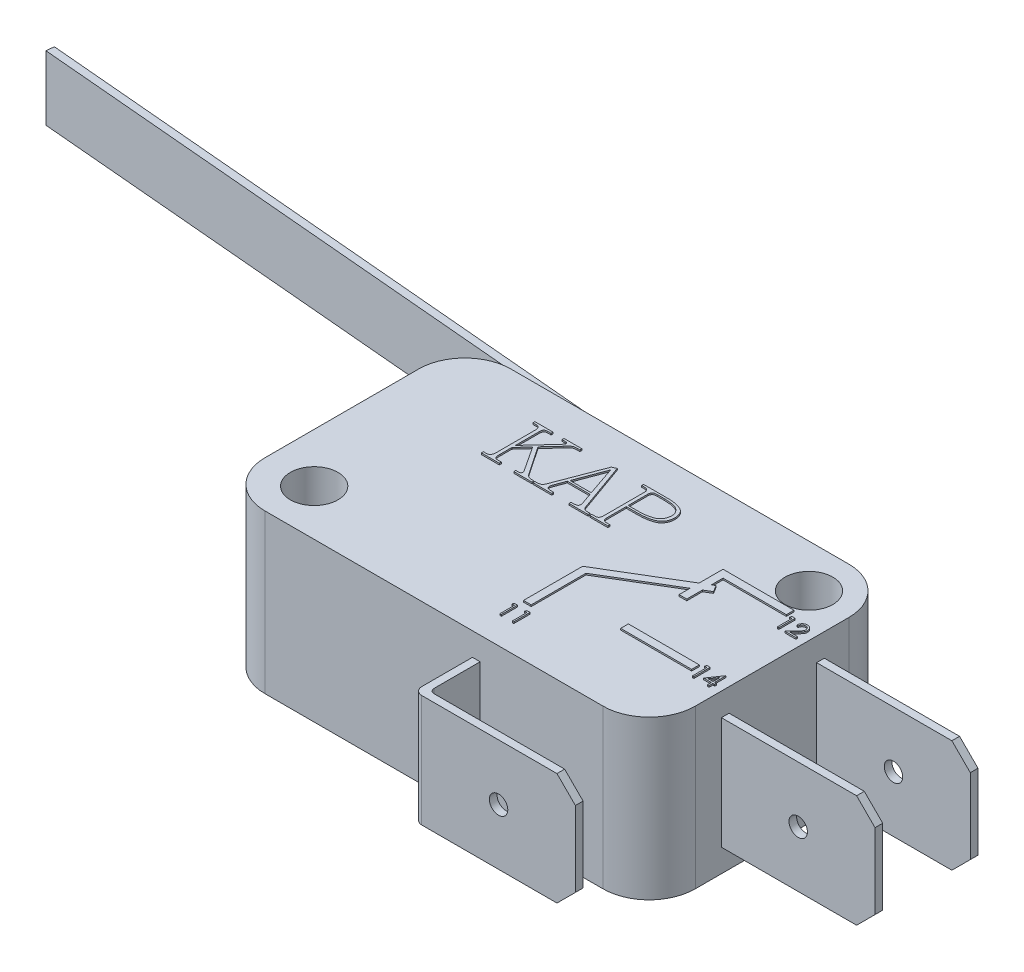
SolidWorks part; units mm, degrees
ref_plane "Plano frontal" through (0, 0, 0) normal (0, 0, 1) x (1, 0, 0)
ref_plane "Plano superior" through (0, 0, 0) normal (0, 1, 0) x (1, 0, 0)
ref_plane "Plano direito" through (0, 0, 0) normal (1, 0, 0) x (0, 0, -1)
sketch "Esboço1" plane through (0, 0, 0) normal (0, 1, 0) x (1, 0, 0)
  line L1 (-68.1435, 2.0444) -> (-40.1435, 2.0444)
  line L2 (-68.1435, 2.0444) -> (-68.1435, -13.9556)
  line L3 (-68.1435, -13.9556) -> (-40.1435, -13.9556)
  line L4 (-40.1435, 2.0444) -> (-40.1435, -13.9556)
extrude "Ressalto-extrusão2" add sketch "Esboço1" along normal blind 10.3
fillet "Filete2" radius 3 1 edges at (-40.1435, 5.15, -2.0444)
fillet "Filete3" radius 3 1 edges at (-40.1435, 5.15, 13.9556)
fillet "Filete4" radius 3 1 edges at (-68.1435, 5.15, -2.0444)
fillet "Filete5" radius 3 1 edges at (-68.1435, 5.15, 13.9556)
sketch "Esboço2" plane through (0, 10.3, 0) normal (0, 1, 0) x (1, 0, 0)
  line L0 (-40.1435, -10.9556) -> (-40.1435, -0.9556) construction
  line L1 (-43.1435, 2.0444) -> (-65.1435, 2.0444) construction
  circle A0 centre (-64.9435, -10.9556) radius 1.55
  circle A1 centre (-42.9435, -0.7556) radius 1.55
  dimension "D1" = 3.1
  dimension "D2" = 3.1
  dimension "D4" = 2.8
  dimension "D5" = 22
  dimension "D6" = 10.2
  dimension "D3" = 2.8
extrude "Corte-extrusão1" cut sketch "Esboço2" against normal blind 10.3
sketch "Esboço3" plane through (-40.1435, 0, 0) normal (1, 0, 0) x (0, 0, -1)
  line L0 (-10.9556, 10.3) -> (-0.9556, 10.3) construction
  line L1 (-2.5556, 8.8) -> (-3.0556, 8.8)
  line L2 (-2.5556, 8.8) -> (-2.5556, 1.5)
  line L3 (-2.5556, 1.5) -> (-3.0556, 1.5)
  line L4 (-3.0556, 8.8) -> (-3.0556, 1.5)
  line L5 (-10.9556, 0) -> (-0.9556, 0) construction
  line L6 (-0.9556, 0) -> (-0.9556, 10.3) construction
  line L8 (-8.7556, 8.8) -> (-9.2556, 8.8)
  line L9 (-8.7556, 8.8) -> (-8.7556, 1.5)
  line L10 (-8.7556, 1.5) -> (-9.2556, 1.5)
  line L11 (-9.2556, 8.8) -> (-9.2556, 1.5)
  line L13 (-10.9556, 10.3) -> (-10.9556, 0) construction
  dimension "D1" = 1.5
  dimension "D2" = 1.5
  dimension "D3" = 1.6
  dimension "D4" = 0.5
  dimension "D5" = 0.5
  dimension "D6" = 5.7
  dimension "D7" = 1.7
extrude "Ressalto-extrusão3" add sketch "Esboço3" along normal blind 10
sketch "Esboço4" plane through (0, 0, 13.9556) normal (0, 0, 1) x (1, 0, 0)
  line L0 (-65.1435, 10.3) -> (-43.1435, 10.3) construction
  line L1 (-51.6435, 8.8) -> (-51.1435, 8.8)
  line L2 (-51.6435, 8.8) -> (-51.6435, 1.5)
  line L3 (-51.6435, 1.5) -> (-51.1435, 1.5)
  line L4 (-51.1435, 8.8) -> (-51.1435, 1.5)
  line L5 (-65.1435, 0) -> (-43.1435, 0) construction
  line L6 (-43.1435, 0) -> (-43.1435, 10.3) construction
  dimension "D1" = 0.5
  dimension "D2" = 1.5
  dimension "D3" = 1.5
  dimension "D4" = 8
extrude "Ressalto-extrusão4" add sketch "Esboço4" along normal blind 3.8
sketch "Esboço5" plane through (-51.1435, 0, 0) normal (1, 0, 0) x (0, 0, -1)
  line L0 (-17.7556, 1.5) -> (-13.9556, 1.5) construction
  line L1 (-17.7556, 8.8) -> (-17.2556, 8.8)
  line L2 (-17.7556, 8.8) -> (-17.7556, 1.5)
  line L3 (-17.7556, 1.5) -> (-17.2556, 1.5)
  line L4 (-17.2556, 8.8) -> (-17.2556, 1.5)
  dimension "D1" = 0.5
extrude "Ressalto-extrusão5" add sketch "Esboço5" along normal blind 10
fillet "Filete8" radius 0.5 1 edges at (-51.6435, 5.15, 17.7556)
fillet "Filete9" radius 0.3 1 edges at (-51.1435, 5.15, 17.2556)
sketch "Esboço6" plane through (0, 0, -2.0444) normal (0, 0, -1) x (-1, 0, 0)
  line L1 (51.4435, 3.05) -> (50.9435, 3.05)
  line L2 (51.4435, 3.05) -> (51.4435, 7.25)
  line L3 (51.4435, 7.25) -> (50.9435, 7.25)
  line L4 (50.9435, 3.05) -> (50.9435, 7.25)
  line L6 (43.1435, 10.3) -> (43.1435, 0) construction
  line L7 (51.4435, 5.15) -> (65.1435, 5.15) construction
  line L8 (65.1435, 0) -> (65.1435, 10.3) construction
  dimension "D1" = 4.2
  dimension "D3" = 0.5
  dimension "D4" = 7.8
extrude "Ressalto-extrusão6" add sketch "Esboço6" along normal blind 2
sketch "Esboço10" plane through (0, 0, -2.0444) normal (0, 0, -1) x (-1, 0, 0)
  line L0 (62.9134, 5.15) -> (65.1435, 5.15) construction
  line L1 (62.9134, 2.9) -> (60.0481, 2.9)
  line L2 (62.9134, 2.9) -> (62.9134, 7.4)
  line L3 (62.9134, 7.4) -> (60.0481, 7.4)
  line L4 (60.0481, 2.9) -> (60.0481, 7.4)
  line L5 (65.1435, 0) -> (65.1435, 10.3) construction
  dimension "D1" = 4.5
extrude "Ressalto-extrusão7" add sketch "Esboço10" along normal blind 1.9
fillet "Filete11" radius 0.6 2 edges at (-60.0481, 5.15, -3.9444) (-62.9134, 5.15, -3.9444)
chamfer "Chanfro1" distance 0.5 angle 5 1 edges at (-51.4435, 5.15, -4.0444) first distance on face at (-51.4435, 5.15, -3.0444)
sketch "Esboço12" plane through (-51.3604, 0, -4.4935) normal (-0.9962, 0, -0.0872) x (-0.0872, 0, 0.9962)
  line L1 (0.4507, 3.05) -> (0.9527, 3.05)
  line L2 (0.4507, 3.05) -> (0.4507, 7.25)
  line L3 (0.4507, 7.25) -> (0.9527, 7.25)
  line L4 (0.9527, 3.05) -> (0.9527, 7.25)
extrude "Ressalto-extrusão8" add sketch "Esboço12" along normal blind 50
chamfer "Chanfro2" distance 1.2 angle 45 6 edges at (-41.1435, 8.8, 17.5056) (-41.1435, 1.5, 17.5056) (-30.1435, 8.8, 9.0056) (-30.1435, 8.8, 2.8056) (-30.1435, 1.5, 9.0056) (-30.1435, 1.5, 2.8056)
sketch "Esboço13" plane through (0, 0, 2.5556) normal (0, 0, -1) x (-1, 0, 0)
  line L0 (30.1435, 5.15) -> (40.1435, 5.15) construction
  line L1 (30.1435, 2.7) -> (30.1435, 7.6) construction
  line L2 (40.1435, 1.5) -> (40.1435, 8.8) construction
  circle A0 centre (35.1435, 5.15) radius 0.6
  dimension "D1" = 1.2
  dimension "D2" = 5
extrude "Corte-extrusão2" cut sketch "Esboço13" against normal blind 10
sketch "Esboço14" plane through (0, 0, 17.7556) normal (0, 0, 1) x (1, 0, 0)
  line L0 (-41.1435, 5.15) -> (-51.1435, 5.15) construction
  line L1 (-41.1435, 7.6) -> (-41.1435, 2.7) construction
  line L2 (-51.1435, 8.8) -> (-51.1435, 1.5) construction
  circle A0 centre (-46.1435, 5.15) radius 0.6
  dimension "D1" = 1.2
extrude "Corte-extrusão3" cut sketch "Esboço14" against normal up to next
sketch "Esboço15" plane through (0, 10.3, 0) normal (0, 1, 0) x (1, 0, 0)
  text T0 "KAP\r\n" font "@Adobe Ming Std L" height 3.5
extrude "Ressalto-extrusão9" add sketch "Esboço15" along normal blind 0.1
sketch "Esboço16" plane through (0, 0, 0) normal (0, -1, 0) x (1, 0, 0)
  text T0 "MV7"
extrude "Corte-extrusão4" cut sketch "Esboço16" against normal blind 0.1
sketch "Esboço17" plane through (0, 0, 0) normal (0, -1, 0) x (1, 0, 0)
  text T0 "15A 250VAC\r\n15(3A) 250~\r\nT85" font "Century Gothic" height in points 5
extrude "Corte-extrusão5" cut sketch "Esboço17" against normal blind 0.1
sketch "Esboço18" plane through (0, 10.3, 0) normal (0, 1, 0) x (1, 0, 0)
  line L0 (-46.8547, -5.2963) -> (-46.8547, -4.5807)
  line L1 (-46.8547, -2.4369) -> (-42.2356, -2.4369)
  line L2 (-42.2356, -9.0985) -> (-46.8547, -9.0985)
  line L3 (-51.5907, -10.6853) -> (-51.5907, -6.8392)
  line L4 (-51.5907, -6.8392) -> (-46.8547, -3.9976)
  line L5 (-51.0907, -10.6853) -> (-51.0907, -7.1223)
  line L6 (-51.0907, -7.1223) -> (-46.8547, -4.5807)
  line L7 (-42.2356, -8.5985) -> (-46.8547, -8.5985)
  line L8 (-46.3547, -5.2963) -> (-46.3547, -4.2807)
  line L9 (-46.3547, -2.9369) -> (-42.2356, -2.9369)
  line L10 (-42.2356, -2.4369) -> (-42.2356, -2.9369)
  line L11 (-42.2356, -8.5985) -> (-42.2356, -9.0985)
  line L12 (-46.8547, -8.5985) -> (-46.8547, -9.0985)
  line L13 (-46.8547, -5.2963) -> (-46.3547, -5.2963)
  line L14 (-46.1609, -3.5813) -> (-45.9036, -4.0101)
  line L15 (-51.5907, -10.6853) -> (-51.0907, -10.6853)
  line L16 (-46.3547, -4.2807) -> (-45.9036, -4.0101)
  line L17 (-46.3547, -3.6976) -> (-46.1609, -3.5813)
  line L18 (-51.0907, -7.1223) -> (-45.9036, -4.0101) construction
  line L19 (-46.8547, -3.9976) -> (-46.8547, -2.4369)
  line L20 (-51.5907, -6.8392) -> (-46.1609, -3.5813) construction
  line L21 (-46.3547, -3.6976) -> (-46.3547, -2.9369)
  line L22 (-46.8547, -5.2963) -> (-46.8547, -2.4369) construction
  line L24 (-46.3547, -5.2963) -> (-46.3547, -2.9369) construction
  dimension "D1" = 0.5
  dimension "D2" = 0.5
extrude "Ressalto-extrusão10" add sketch "Esboço18" along normal blind 0.1
sketch "Esboço20" plane through (0, 10.3, 0) normal (0, 1, 0) x (1, 0, 0)
  text T0 "                         12\r\n\r\n                         14\r\n 11\r\n" font "Century Gothic" height in points 4
  point P1 (-55.5192, -11.4365)
  point P2 (-83.2683, -20.2104)
  point P3 (-57.3478, -1.7444)
  point P4 (-52.7284, -1.0342)
  point P5 (0, 0)
  point P6 (-52.6597, -2.6952)
  point P7 (0, 0)
  point P8 (-51.9226, -3.1559)
  point P9 (0, 0)
  point P10 (0, 0)
  point P11 (-52.2451, -3.1559)
extrude "Ressalto-extrusão11" add sketch "Esboço20" along normal blind 0.1
